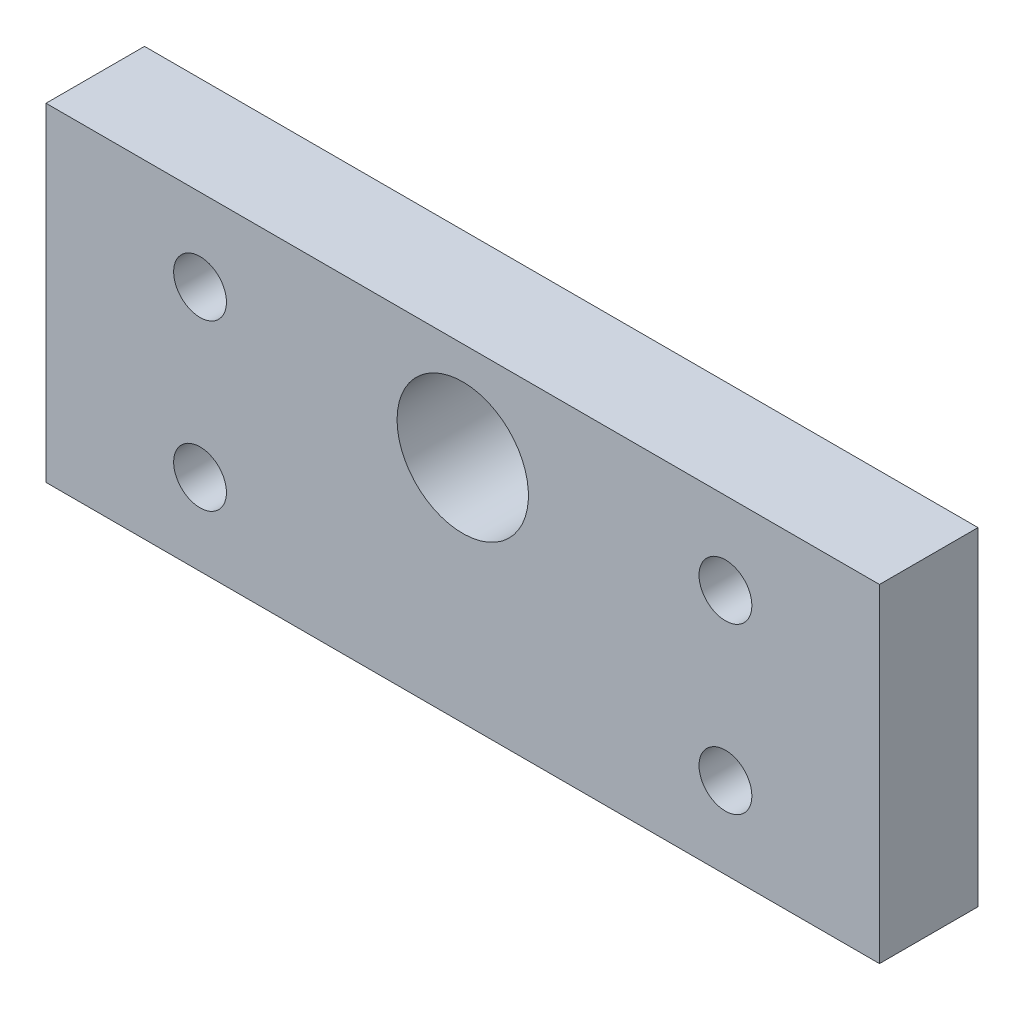
SolidWorks part; units mm, degrees
material "6061-T6 (SS)"
ref_plane "Front Plane" through (0, 0, 0) normal (0, 0, 1) x (1, 0, 0)
ref_plane "Top Plane" through (0, 0, 0) normal (0, 1, 0) x (1, 0, 0)
ref_plane "Right Plane" through (0, 0, 0) normal (1, 0, 0) x (0, 0, -1)
sketch "Sketch1" plane through (0, 0, 0) normal (0, 0, 1) x (1, 0, 0)
  line L2 (40.2927, 0) -> (-40.2927, 0)
  line L3 (40.2927, 0) -> (40.2927, 31.75)
  line L4 (40.2927, 31.75) -> (-40.2927, 31.75)
  line L6 (-40.2927, 0) -> (-40.2927, 31.75)
  circle A0 centre (0, 22.225) radius 6.35
  point P6 (0, 0)
  line B0 (63.5, 0) -> (63.5, 15.875)
  line B1 (63.5, 15.875) -> (38.4596, 15.875)
  line B2 (38.4596, 15.875) -> (47.625, 31.75)
  line B3 (47.625, 31.75) -> (16.0563, 31.75)
  line B4 (-16.0563, 31.75) -> (-16.0563, 12.7)
  line B5 (16.0563, 12.7) -> (16.0563, 31.75)
  line B6 (-63.5, 47.625) -> (63.5, 47.625)
  line B7 (63.5, 47.625) -> (63.5, 15.875)
  line B8 (0, 47.625) -> (0, 0) construction
  line B9 (-38.4596, 15.875) -> (38.4596, 15.875) construction
  line B10 (-28.702, 36.957) -> (28.702, 36.957) construction
  line B11 (-25.4, 7.874) -> (25.4, 7.874) construction
  line B12 (-25.4, 7.874) -> (-25.4, 23.8125) construction
  line B13 (25.4, 7.874) -> (25.4, 23.8125) construction
  line B14 (-52.832, 23.8125) -> (52.832, 23.8125) construction
  circle B15 centre (0, 22.225) radius 18.669 construction
  dimension "D1" = 12.7
sketch_block_instance "dovetail pair-1"
sketch_block "dovetail pair" parameters "D8"=37.338, "D1"=60, "D2"=127, "D3"=6.35, "D4"=15.875, "D5"=31.75, "D6"=95.25, "D7"=19.05, "D9"=60, "D10"=31.75, "D11"=50.8, "D12"=23.876, "D13"=7.874, "D14"=10.668, "D15"=34.798, "D16"=21.082, "D17"=7.9375
extrude "Boss-Extrude1" add sketch "Sketch1" along normal blind 9.525
hole_wizard "CBORE for #10 Socket Head Cap Screw1" positions "Sketch2" profile "Sketch3" counterbore size "#10" standard "ANSI Inch" end condition up to next
sketch "Sketch2" plane through (0, 0, 0) normal (0, 0, 1) x (1, 0, 0)
  point P27 (25.4, 23.8125)
  point P29 (-25.4, 23.8125)
  point P31 (-25.4, 7.874)
  point P33 (25.4, 7.874)
sketch "Sketch3" plane through (25.4, 23.8125, 0) normal (1, 0, 0) x (0, 1, 0)
  line L0 (0, 0) -> (0, 9.525)
  line L1 (0, 9.525) -> (2.5527, 9.525)
  line L3 (2.5527, 9.525) -> (2.5527, 4.826)
  line L4 (4.7625, 4.826) -> (2.5527, 4.826)
  line L5 (4.7625, 4.826) -> (4.7625, 0.635)
  line L6 (4.7625, 0.635) -> (5.3975, 0)
  line L7 (5.3975, 0) -> (0, 0)
  line L8 (-4.7625, 0.635) -> (-5.3975, 0) construction
  line L11 (0, -6.35) -> (0, 107.95) construction
  dimension "Thru Hole Dia." = 5.1054
  dimension "Thru Hole Depth" = 9.525
  dimension "C'Bore Dia." = 9.525
  dimension "C'Bore Depth" = 4.826
  dimension "Near C'Sink Dia." = 10.795
  dimension "Near C'Sink Angle" = 90
ref_plane "center plane" through (0, 0, 0) normal (1, 0, 0) x (0, 0, -1)
equation "\"dovetail-angle\" = 60"
equation "\"dovetail-stock-width\" = 5"
equation "\"dovetail-stock-height\" = 1.25"
equation "\"dovetail-depth\" = 0.5 * \"dovetail-stock-height\""
equation "\"dovetail-throat-width\" = \"dovetail-stock-width\" - (2 * \"dovetail-depth\")"
equation "\"delta-x\" = 6"
equation "\"delta-y\" = 3"
equation "\"gib-thickness\" = 0.25"
equation "\"x-slide-length\" = \"dovetail-stock-width\" + \"delta-x\""
equation "\"y-slide-length\" = \"dovetail-stock-width\" + \"delta-y\""
equation "\"dog-point-diam\" = .149"
equation "\"dog-point-length\" = .067"
equation "\"dovetail-double-height\" = 2 * \"dovetail-depth\" + 0.5"
equation "\"acme-major-diam\" = .5"
equation "\"acme-pitch-diam\" = 0.45"
equation "\"acme-minor-diam\" = 0.4"
equation "\"acme-nut-od\" = 1.47"
equation "\"acme-nut-length\" = 1"
equation "\"acme-nut-trim-height\" = .75"
equation "\"screw-bearing-od\" = 0.5"
equation "\"screw-bearing-length\" = .375"
equation "\"screw-bearing-id\" = .375"
equation "\"end-plate-thickness\" = \"screw-bearing-length\""
equation "\"screw-add-length\" = 2 * \"end-plate-thickness\" + 1 + 0.5"
equation "\"x-screw-length\" = \"x-slide-length\" + \"screw-add-length\""
equation "\"y-screw-length\" = \"y-slide-length\" + \"screw-add-length\""
equation "\"acme-nut-mount-hole-space-horz\" = 0.95"
equation "\"acme-nut-mount-hole-space-vert\" = 0.5 * \"acme-nut-length\""
equation "\"vise-hole-center-dist\" = 6.75"
equation "\"wiper_plate_clearance\" = .03"
equation "\"D1@Boss-Extrude1\"=\"screw-bearing-length\""
equation "\"D2@dovetail pair\"=\"dovetail-stock-width\""
equation "\"D1@dovetail pair\"=\"dovetail-angle\""
equation "\"D3@dovetail pair\"=\"gib-thickness\""
equation "\"D4@dovetail pair\"=\"dovetail-depth\""
equation "\"D5@dovetail pair\"=\"dovetail-stock-height\""
equation "\"D6@dovetail pair\"=\"dovetail-throat-width\""
equation "\"D10@dovetail pair\"=\"dovetail-stock-height\""
equation "\"D7@dovetail pair\"=\"acme-nut-trim-height\""
equation "\"D8@dovetail pair\"=\"acme-nut-od\""
equation "\"D9@dovetail pair\"=\"dovetail-angle\""
equation "\"D17@dovetail pair\"=\"dovetail-depth\"/2"
equation "\"D1@Sketch1\"=\"screw-bearing-od\""
